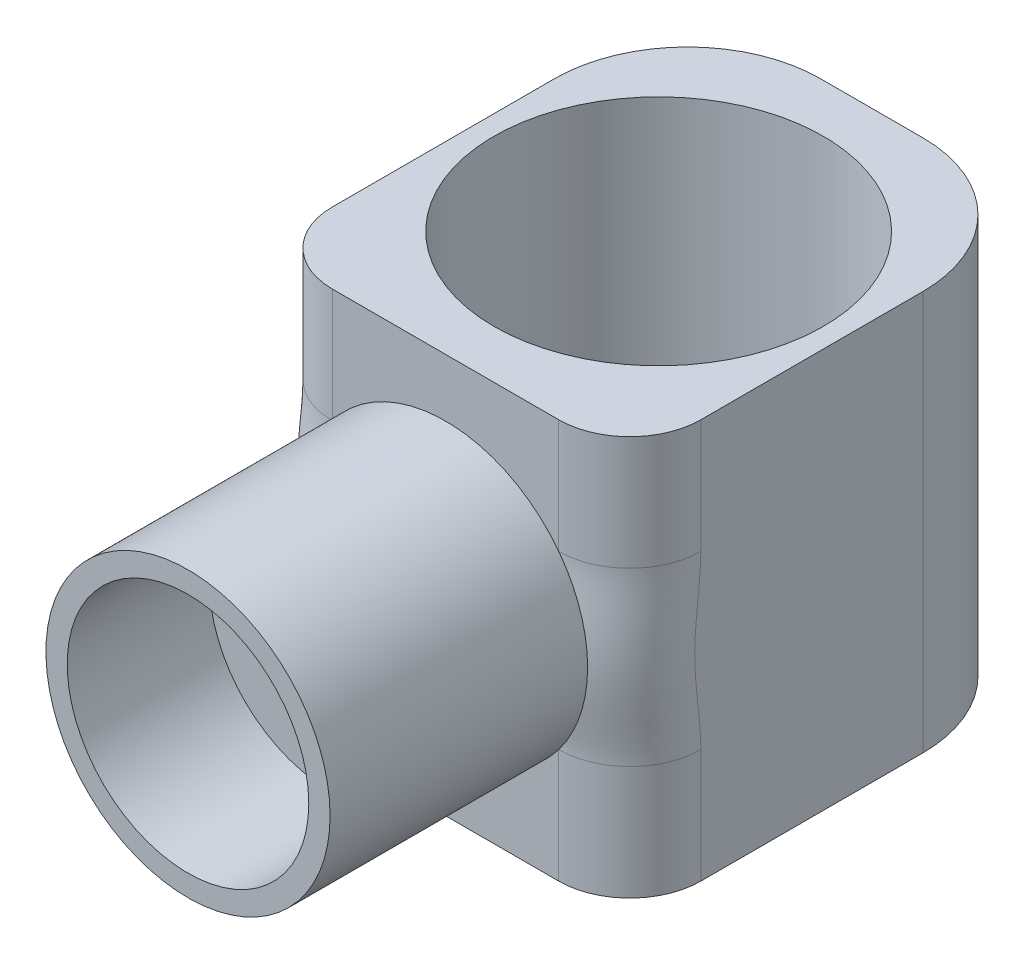
SolidWorks part; units mm, degrees
ref_plane "Alzado" through (0, 0, 0) normal (0, 0, 1) x (1, 0, 0)
ref_plane "Planta" through (0, 0, 0) normal (0, 1, 0) x (1, 0, 0)
ref_plane "Vista lateral" through (0, 0, 0) normal (1, 0, 0) x (0, 0, -1)
sketch "Croquis1" plane through (0, 0, 0) normal (0, 0, 1) x (1, 0, 0)
  circle A0 centre (0, 0) radius 16
  dimension "D1" = 32
extrude "Saliente-Extruir1" add sketch "Croquis1" along normal blind 13
sketch "Croquis2" plane through (0, 0, 13) normal (0, 0, 1) x (1, 0, 0)
  circle A0 centre (0, 0) radius 16
  circle A1 centre (0, 0) radius 13.6
  dimension "D1" = 27.2
  dimension "D2" = 32
extrude "Saliente-Extruir2" add sketch "Croquis2" along normal blind 16
sketch "Croquis3" plane through (0, 0, 0) normal (0, 0, -1) x (-1, 0, 0)
  line L0 (0, 0) -> (-9.3251, 0) construction
  line L1 (0, 0) -> (0, 10.2392) construction
  line L2 (20.75, 22.5) -> (-20.75, 22.5)
  line L3 (-20.75, 22.5) -> (-20.75, -22.5)
  line L4 (20.75, 22.5) -> (20.75, -22.5)
  line L5 (20.75, -22.5) -> (-20.75, -22.5)
  point P12 (0, 22.5)
  point P13 (20.75, 0)
  point P14 (-20.75, 0)
  dimension "D1" = 20.75
  dimension "D2" = 22.5
extrude "Saliente-Extruir3" add sketch "Croquis3" along normal blind 48
sketch "Croquis5" plane through (0, 22.5, 0) normal (0, 1, 0) x (1, 0, 0)
  line L0 (-20.75, 24) -> (20.75, 24) construction
  line L1 (-20.75, 48) -> (-20.75, 0) construction
  line L2 (20.75, 48) -> (20.75, 0) construction
  circle A0 centre (0, 24) radius 18.55
  dimension "D1" = 37.1
extrude "Cortar-Extruir1" cut sketch "Croquis5" against normal blind 29.5
sketch "Croquis6" plane through (0, -7, 0) normal (0, 1, 0) x (1, 0, 0)
  circle A0 centre (0, 24) radius 16.55
  dimension "D1" = 33.1
extrude "Cortar-Extruir2" cut sketch "Croquis6" against normal up to surface (15.5 mm away) up to face at (0, -22.5, -24)
fillet "Redondeo1" radius 15 2 edges at (-20.75, 0, -48) (20.75, 0, -48)
fillet "Redondeo2" radius 8 2 edges at (-20.75, 0, 0) (20.75, 0, 0)
